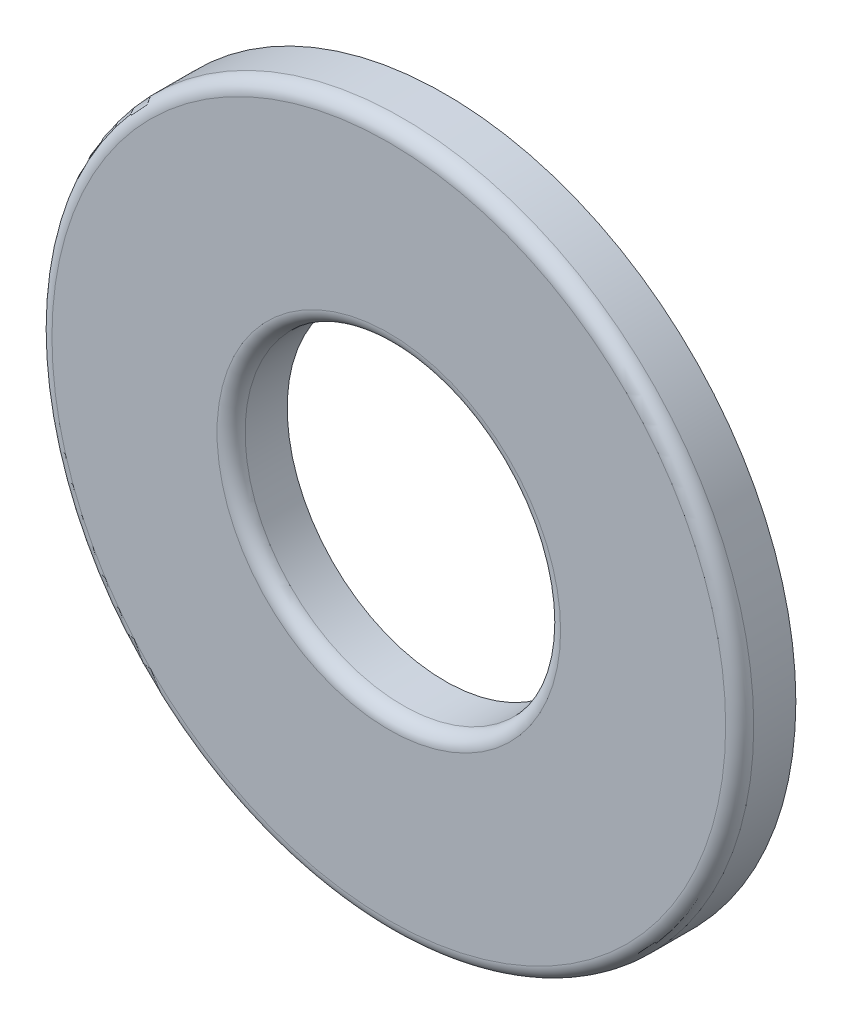
SolidWorks part; units mm, degrees
material "Plain Carbon Steel"
ref_plane "Front Plane" through (0, 0, 0) normal (0, 0, 1) x (1, 0, 0)
ref_plane "Top Plane" through (0, 0, 0) normal (0, 1, 0) x (1, 0, 0)
ref_plane "Right Plane" through (0, 0, 0) normal (1, 0, 0) x (0, 0, -1)
sketch "Sketch1" plane through (0, 0, 0) normal (0, 0, 1) x (1, 0, 0)
  line L0 (-7.9375, 0) -> (7.9375, 0) construction
  line L1 (-3.5687, 0) -> (3.5687, 0) construction
  circle A0 centre (0, 0) radius 3.5687 construction
  circle A1 centre (0, 0) radius 7.9375 construction
  point P8 (0, 0)
  point P9 (0, 7.9375)
  point P11 (3.5687, 0)
  dimension "ID" = 7.1374
  dimension "OD" = 15.875
sketch "Sketch2" plane through (0, 0, 0) normal (1, 0, 0) x (0, 0, -1)
  line L0 (-0.635, 7.9375) -> (0.635, 7.9375) construction
  point P2 (0, 7.9375)
  dimension "Thickness" = 1.27
sketch "Sketch3" plane through (0, 0, 0) normal (0, 0, 1) x (1, 0, 0)
  circle A0 centre (0, 0) radius 3.5687
  circle A1 centre (0, 0) radius 7.9375
extrude "Boss-Extrude1" add sketch "Sketch3" along normal up to vertex (0.635 mm away) and the other way up to vertex (0.635 mm away) up to point (0, 7.9375, 0.635) other way up to point (0, 7.9375, -0.635)
fillet "Fillet1" radius 0.3175 2 edges at (7.9375, 0, 0.635) (3.5687, 0, 0.635)
ref_axis "Center Axis 1" through (0, 0, 0.3175) along (0, 0, -1)
